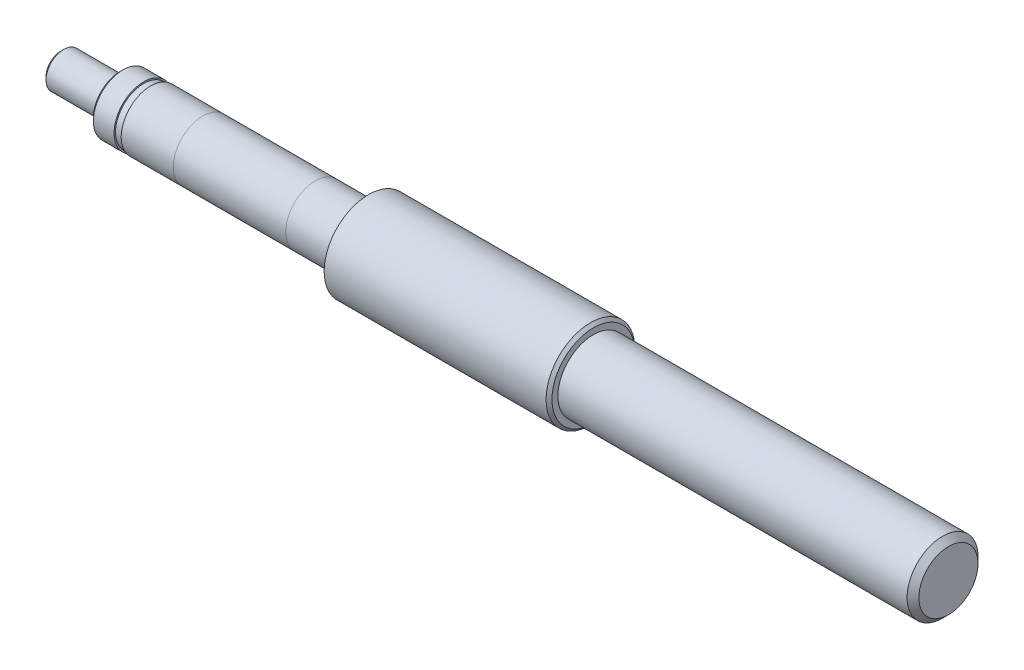
SolidWorks part; units mm, degrees
material "Сталь 45 ГОСТ 1050-88"
ref_plane "Front Plane" through (0, 0, 0) normal (0, 0, 1) x (1, 0, 0)
ref_plane "Top Plane" through (0, 0, 0) normal (0, 1, 0) x (1, 0, 0)
ref_plane "Right Plane" through (0, 0, 0) normal (1, 0, 0) x (0, 0, -1)
sketch "Skizze1" plane through (0, 0, 0) normal (0, 1, 0) x (1, 0, 0)
  line L0 (-7, 0) -> (-7, 2.5)
  line L1 (-7, 0) -> (-7, -2.5)
  line L2 (-7, 0) -> (-7, 2.5)
  line L4 (-7, 0) -> (-7, -2.5)
  line L9 (3, 0) -> (3, 4.5)
  line L13 (3.5, 5) -> (7, 5)
  line L14 (3, 0) -> (3, -4.5)
  line L30 (65, 0) -> (-7, 0)
  line L35 (7, -5) -> (7, -4.75)
  line L36 (7, 5) -> (7, -5)
  line L44 (82.5, -7.5) -> (83, -7)
  line L45 (7, 5) -> (7, 4.75)
  line L46 (82.5, 7.5) -> (83, 7)
  line L47 (45, 0) -> (45, 7.5)
  line L48 (45, 7.5) -> (82.5, 7.5)
  line L49 (45, -7.5) -> (82.5, -7.5)
  line L50 (83, -7) -> (83, 7)
  line L51 (143, 5) -> (142, 6)
  line L52 (-7, 0) -> (-7, 2.5)
  line L56 (143, -5) -> (142, -6)
  line L57 (65, 0) -> (143, 0)
  line L59 (143, 0) -> (143, -5)
  line L60 (142, -6) -> (83, -6)
  line L64 (-6.5, 3) -> (3, 3)
  line L65 (3, 3) -> (3, 0)
  line L66 (3, 0) -> (3, -3)
  line L67 (3, -3) -> (-6.5, -3)
  line L68 (-7, -2.5) -> (-7, 0)
  line L69 (-7, 2.5) -> (-6.5, 3)
  line L70 (-6.5, -3) -> (-7, -2.5)
  line L71 (3.5, -5) -> (7, -5)
  line L72 (3, 4.5) -> (3.5, 5)
  line L73 (3, -4.5) -> (3.5, -5)
  line L74 (8.0557, 4.75) -> (8.0557, 0)
  line L75 (44.7, -4.85) -> (44.0828, -4.85)
  line L76 (8.0557, 4.75) -> (8.2, 5)
  line L77 (8.2, -5) -> (8.2, 5)
  line L78 (8.0557, -4.75) -> (8.2, -5)
  line L79 (8.0557, -4.75) -> (8.0557, 0)
  line L80 (8.0557, 4.75) -> (7, 4.75)
  line L81 (8.0557, -4.75) -> (7, -4.75)
  line L82 (8.2, 5) -> (43.85, 5)
  line L83 (8.2, -5) -> (43.85, -5)
  line L84 (43.85, 5) -> (43.9414, 4.9086)
  line L85 (44.7, 4.85) -> (44.0828, 4.85)
  line L86 (43.85, -5) -> (43.9414, -4.9086)
  line L87 (45, 0) -> (45, -7.5)
  line L88 (143, 0) -> (143, 5)
  line L89 (142, 6) -> (83, 6)
  arc A6 (44.7, 4.85) -> (45, 5.15) centre (44.7, 5.15) ccw
  arc A7 (43.9414, 4.9086) -> (44.0828, 4.85) centre (44.0828, 5.05) ccw
  arc A8 (43.9414, -4.9086) -> (44.0828, -4.85) centre (44.0828, -5.05) cw
  arc A9 (44.7, -4.85) -> (45, -5.15) centre (44.7, -5.15) cw
  point P4 (68, 7.5)
  point P5 (10, 5)
  point P7 (10, -5)
  point P17 (68, -7.5)
  point P24 (92, -6)
  point P29 (92, 6)
  point P36 (69, 6)
  point P81 (15.3443, 0)
revolve "Rotation1" add sketch "Skizze1" angle 360 about L57 region at (-1.9798, 0, -1.4944) region at (5.0115, 0, -2.4853) region at (7.5278, 0, -2.375) region at (8.1284, 0, -2.438) region at (26.5863, 0, -2.4981) region at (63.9917, 0, -3.7484) region at (112.9587, 0, -2.9963)
sketch "Эскиз1" plane through (0, 0, 0) normal (0, 1, 0) x (1, 0, 0)
  line L2 (17, -5) -> (17, 5)
  line L4 (3, 6.7617) -> (3, -6.7617)
  line L6 (36, -7.5) -> (36, 7.5)
split line "Разделяющая линия1"
